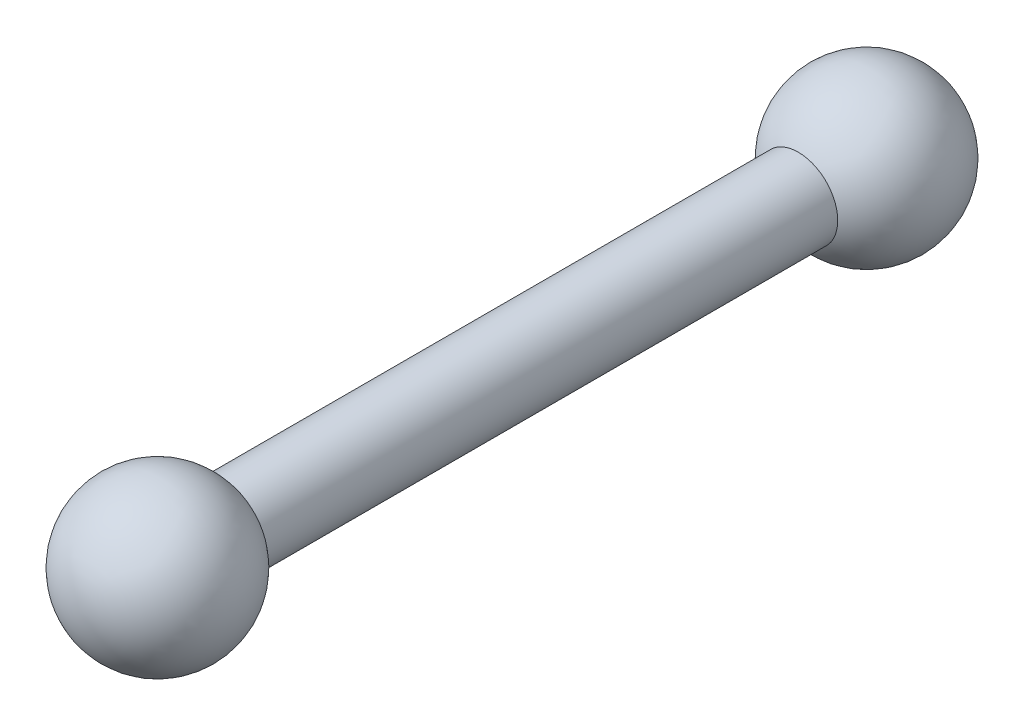
SolidWorks part; units mm, degrees
ref_plane "Front Plane" through (0, 0, 0) normal (0, 0, 1) x (1, 0, 0)
ref_plane "Top Plane" through (0, 0, 0) normal (0, 1, 0) x (1, 0, 0)
ref_plane "Right Plane" through (0, 0, 0) normal (1, 0, 0) x (0, 0, -1)
sketch "Sketch1" plane through (0, 0, 0) normal (0, 0, 1) x (1, 0, 0)
  circle A0 centre (0, 0) radius 2
  dimension "D1" = 4
extrude "Boss-Extrude1" add sketch "Sketch1" against normal blind 30
ref_plane "Plane1" through (0, 0, 3) normal (0, 0, 1) x (1, 0, 0)
sketch "Sketch2" plane through (0, 0, 3) normal (0, 0, 1) x (1, 0, 0)
  line L0 (0, 4) -> (0, -4) construction
  line L1 (0, 4) -> (0, -4)
  arc A1 (0, -4) -> (0, 4) centre (0, 0) ccw
  dimension "D1" = 8
revolve "Revolve1" add sketch "Sketch2" angle 360 about L0
ref_plane "Plane2" through (0, 0, -15) normal (0, 0, 1) x (1, 0, 0)
mirror "Mirror2" about plane through (0, 0, -15) normal (0, 0, 1) of "Revolve1"
